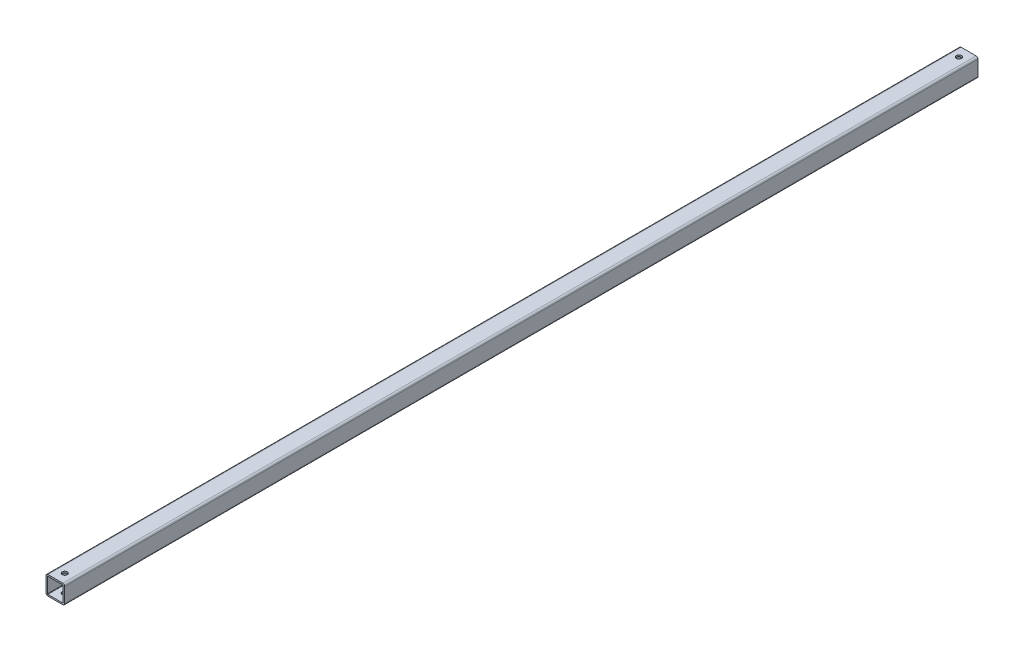
SolidWorks part; units mm, degrees
material "Galvanized Steel"
ref_plane "Front Plane" through (0, 0, 0) normal (0, 0, 1) x (1, 0, 0)
ref_plane "Top Plane" through (0, 0, 0) normal (0, 1, 0) x (1, 0, 0)
ref_plane "Right Plane" through (0, 0, 0) normal (1, 0, 0) x (0, 0, -1)
sketch "Sketch1" plane through (0, 0, 0) normal (0, 0, 1) x (1, 0, 0)
  line L1 (10, -12.5) -> (-10, -12.5)
  line L2 (12.5, -10) -> (12.5, 10)
  line L3 (10, 12.5) -> (-10, 12.5)
  line L4 (-12.5, -10) -> (-12.5, 10)
  line L5 (12.5, -12.5) -> (-12.5, 12.5) construction
  line L6 (12.5, 12.5) -> (-12.5, -12.5) construction
  arc A0 (-10, 12.5) -> (-12.5, 10) centre (-10, 10) ccw
  arc A1 (12.5, 10) -> (10, 12.5) centre (10, 10) ccw
  arc A2 (10, -12.5) -> (12.5, -10) centre (10, -10) ccw
  arc A3 (-10, -12.5) -> (-12.5, -10) centre (-10, -10) cw
  point P0 (0, 0)
  dimension "D2" = 2.5
  dimension "D1" = 25
extrude "Extrude-Thin1" add sketch "Sketch1" along normal mid plane 1219.2 thin thin type one direction reverse wall 2
hole_wizard "1/4 Clearance Hole1" positions "Sketch2" profile "Sketch3" hole size "1/4" standard "ANSI Inch"
sketch "Sketch2" plane through (0, 12.5, 0) normal (0, 1, 0) x (1, 0, 0)
  line L0 (12.5, -609.6) -> (12.5, 609.6) construction
  line L1 (10, 609.6) -> (-10, 609.6) construction
  line L2 (10, -609.6) -> (-10, -609.6) construction
  point P0 (-0.2, 596.9)
  point P7 (-0.2, -596.9)
  dimension "D1" = 12.7
  dimension "D2" = 12.7
  dimension "D3" = 12.7
  dimension "D4" = 12.7
sketch "Sketch3" plane through (-0.2, 12.5, -596.9) normal (1, 0, 0) x (0, 0, 1)
  line L0 (0, 0) -> (0, 27.4298)
  line L1 (0, 27.4298) -> (3.3782, 25.4)
  line L2 (3.3782, 25.4) -> (3.3782, 0)
  line L5 (3.3782, 0) -> (0, 0)
  line L10 (0, 27.4298) -> (-3.3782, 25.4) construction
  line L11 (0, -6.35) -> (0, 107.95) construction
  dimension "Hole Dia." = 6.7564
  dimension "Hole Depth" = 25.4
  dimension "Drill Angle" = 118
equation "\"D2@Sketch1\" = \"D5@Extrude-Thin1\" * 1.25"
